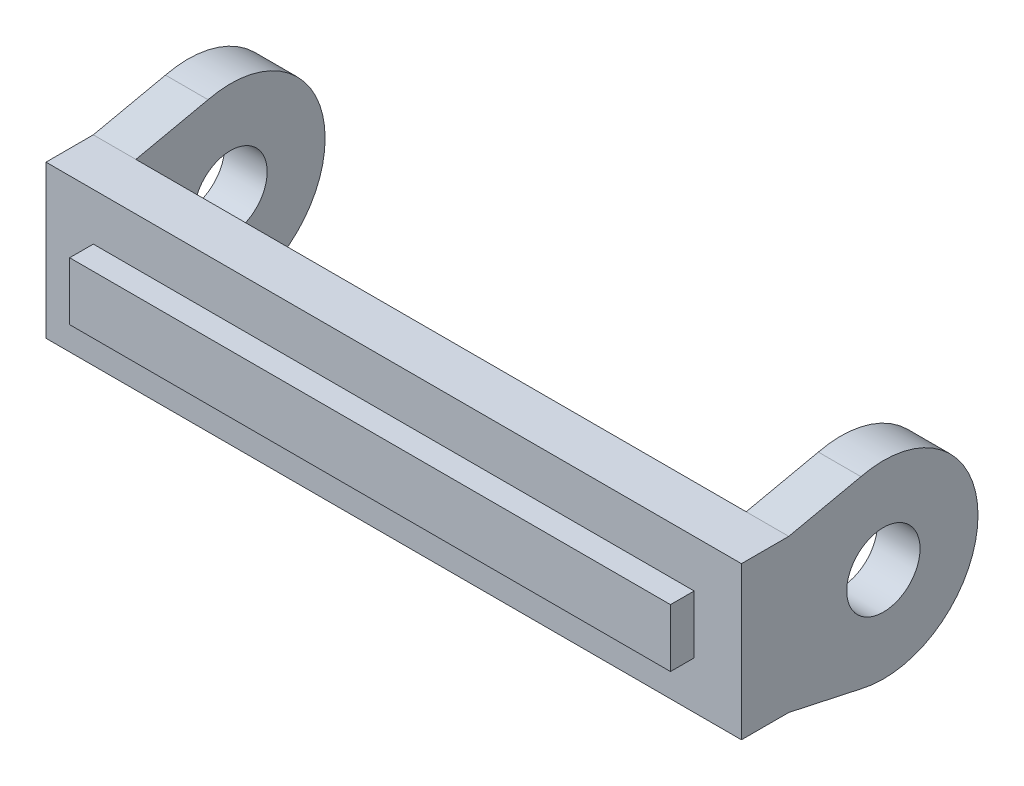
SolidWorks part; units mm, degrees
ref_plane "Alzado" through (0, 0, 0) normal (0, 0, 1) x (1, 0, 0)
ref_plane "Planta" through (0, 0, 0) normal (0, 1, 0) x (1, 0, 0)
ref_plane "Vista lateral" through (0, 0, 0) normal (1, 0, 0) x (0, 0, -1)
sketch "Croquis1" plane through (0, 0, 0) normal (0, 0, 1) x (1, 0, 0)
  line L1 (-35.9671, 18.9928) -> (-9.5671, 18.9928)
  line L2 (-35.9671, 18.9928) -> (-35.9671, 16.0428)
  line L3 (-35.9671, 16.0428) -> (-9.5671, 16.0428)
  line L4 (-9.5671, 18.9928) -> (-9.5671, 16.0428)
  dimension "D1" = 26.4
  dimension "D2" = 2.95
extrude "Saliente-Extruir1" add sketch "Croquis1" along normal blind 1.5
sketch "Croquis2" plane through (-9.5671, 0, 0) normal (1, 0, 0) x (0, 0, -1)
  line L2 (0, 16.0428) -> (0, 18.9928) construction
  line L3 (0, 18.9928) -> (0.3876, 18.9928)
  line L4 (0, 16.0428) -> (0.3876, 16.0428)
  line L6 (-1.5, 16.0428) -> (0, 16.0428) construction
  line L7 (0, 18.9928) -> (-0.5, 18.9928)
  line L9 (0, 16.0428) -> (-0.5, 16.0428)
  line L10 (-0.5, 18.9928) -> (-0.5, 16.0428)
  arc A0 (0.3876, 16.0428) -> (0.3876, 18.9928) centre (3, 17.5178) ccw
  dimension "D1" = 6
  dimension "D2" = 3
  dimension "D3" = 0.5
extrude "Saliente-Extruir2" add sketch "Croquis2" along normal blind 1
sketch "Croquis3" plane through (-35.9671, 0, 0) normal (-1, 0, 0) x (0, 0, 1)
  line L0 (0, 18.9928) -> (0, 16.0428) construction
  line L1 (1.5, 18.9928) -> (0, 18.9928) construction
  line L2 (0.5, 18.9928) -> (-0.3876, 18.9928)
  line L3 (0.5, 18.9928) -> (0.5, 16.0428)
  line L4 (0.5, 16.0428) -> (-0.3876, 16.0428)
  arc A0 (-0.3876, 18.9928) -> (-0.3876, 16.0428) centre (-3, 17.5178) ccw
  dimension "D1" = 6
  dimension "D2" = 3
  dimension "D3" = 0.5
extrude "Saliente-Extruir3" add sketch "Croquis3" along normal blind 1
sketch "Croquis5" plane through (0, 18.9928, 0) normal (0, 1, 0) x (1, 0, 0)
  line L1 (-35.9671, 0.3876) -> (-9.5671, 0.3876)
  line L2 (-35.9671, 0.3876) -> (-35.9671, 0)
  line L3 (-35.9671, 0) -> (-9.5671, 0)
  line L4 (-9.5671, 0.3876) -> (-9.5671, 0)
extrude "Saliente-Extruir4" add sketch "Croquis5" against normal up to surface (2.95 mm away) up to face at (-22.7671, 16.0428, 0.2875)
sketch "Croquis7" plane through (-8.5671, 0, 0) normal (1, 0, 0) x (0, 0, -1)
  circle A0 centre (3, 17.5178) radius 1.5
  dimension "D1" = 3
extrude "Cortar-Extruir1" cut sketch "Croquis7" against normal blind 51
sketch "Croquis8" plane through (-9.5671, 0, 0) normal (-1, 0, 0) x (0, 0, 1)
  circle A0 centre (-3, 17.5178) radius 3
extrude "Cortar-Extruir2" cut sketch "Croquis8" along normal up to surface (26.4 mm away) up to face at (-35.9671, 17.5178, -1.5)
sketch "Croquis9" plane through (0, 0, 0) normal (0, 1, 0) x (1, 0, 0)
  line L0 (-36.9671, -0.5) -> (-35.9671, -0.5) construction
  line L1 (-36.7671, -0.5) -> (-37.2671, -0.5)
  line L2 (-36.7671, -0.5) -> (-36.7671, -1.5)
  line L3 (-36.7671, -1.5) -> (-37.2671, -1.5)
  line L4 (-37.2671, -0.5) -> (-37.2671, -1.5)
  line L5 (-36.9671, -0.5) -> (-36.9671, 0.3876) construction
  line L6 (-8.5671, -0.5) -> (-9.5671, -0.5) construction
  line L7 (-8.7687, -0.5) -> (-8.2687, -0.5)
  line L8 (-8.7687, -0.5) -> (-8.7687, -1.5)
  line L9 (-8.7687, -1.5) -> (-8.2687, -1.5)
  line L10 (-8.2687, -0.5) -> (-8.2687, -1.5)
  line L11 (-8.5671, 0.3876) -> (-8.5671, -0.5) construction
  dimension "D1" = 0.2
  dimension "D2" = 0.5
  dimension "D3" = 0.2017
  dimension "D4" = 0.5
extrude "Saliente-Extruir5" add sketch "Croquis9" along normal blind 20
sketch "Croquis11" plane through (-37.2671, 0, 0) normal (-1, 0, 0) x (0, 0, 1)
  line L1 (0.5, 18.9928) -> (1.5, 18.9928)
  line L2 (0.5, 18.9928) -> (0.5, 20)
  line L3 (0.5, 20) -> (1.5, 20)
  line L4 (1.5, 18.9928) -> (1.5, 20)
  line L5 (0.5, 16.0428) -> (1.5, 16.0428)
  line L6 (0.5, 16.0428) -> (0.5, 0)
  line L7 (0.5, 0) -> (1.5, 0)
  line L8 (1.5, 16.0428) -> (1.5, 0)
extrude "Cortar-Extruir3" cut sketch "Croquis11" against normal blind 40
sketch "Croquis13" plane through (0, 0, 1.5) normal (0, 0, 1) x (1, 0, 0)
  line L0 (-9.5671, 18.9928) -> (-35.9671, 18.9928) construction
  line L1 (-35.4671, 18.7428) -> (-10.0671, 18.7428)
  line L2 (-35.4671, 18.7428) -> (-35.4671, 16.2928)
  line L3 (-35.4671, 16.2928) -> (-10.0671, 16.2928)
  line L4 (-10.0671, 18.7428) -> (-10.0671, 16.2928)
  line L5 (-35.9671, 16.0428) -> (-9.5671, 16.0428) construction
  line L6 (-35.9671, 18.9928) -> (-35.9671, 16.0428) construction
  line L7 (-9.5671, 18.9928) -> (-9.5671, 16.0428) construction
  dimension "D1" = 0.25
  dimension "D2" = 0.25
  dimension "D3" = 0.5
  dimension "D4" = 0.5
extrude "Saliente-Extruir6" add sketch "Croquis13" along normal blind 1
sketch "Croquis14" plane through (0, 18.9928, 0) normal (0, 1, 0) x (1, 0, 0)
  line L1 (-35.9671, -0.5) -> (-40.4942, -0.5)
  line L2 (-35.9671, -0.5) -> (-35.9671, -2.0892)
  line L3 (-35.9671, -2.0892) -> (-40.4942, -2.0892)
  line L4 (-40.4942, -0.5) -> (-40.4942, -2.0892)
  line L5 (-9.5671, -0.5) -> (-6.2413, -0.5)
  line L6 (-9.5671, -0.5) -> (-9.5671, -2.6891)
  line L7 (-9.5671, -2.6891) -> (-6.2413, -2.6891)
  line L8 (-6.2413, -0.5) -> (-6.2413, -2.6891)
extrude "Cortar-Extruir4" cut sketch "Croquis14" against normal blind 21
sketch "Croquis16" plane through (0, 18.9928, 0) normal (0, 1, 0) x (1, 0, 0)
  line L1 (-7.5159, -1.5) -> (-41.9143, -1.5)
  line L2 (-7.5159, -1.5) -> (-7.5159, 7.9216)
  line L3 (-7.5159, 7.9216) -> (-41.9143, 7.9216)
  line L4 (-41.9143, -1.5) -> (-41.9143, 7.9216)
extrude "Cortar-Extruir5" cut sketch "Croquis16" against normal blind 21 and the other way blind 21
sketch "Croquis17" plane through (0, 0, 1.5) normal (0, 0, -1) x (-1, 0, 0)
  line L0 (10.0671, 18.7428) -> (35.4671, 18.7428) construction
  line L1 (8.0671, 20.7428) -> (37.4671, 20.7428)
  line L2 (8.0671, 20.7428) -> (8.0671, 14.2928)
  line L3 (8.0671, 14.2928) -> (37.4671, 14.2928)
  line L4 (37.4671, 20.7428) -> (37.4671, 14.2928)
  line L5 (35.4671, 16.2928) -> (10.0671, 16.2928) construction
  line L6 (10.0671, 16.2928) -> (10.0671, 18.7428) construction
  line L7 (35.4671, 18.7428) -> (35.4671, 16.2928) construction
  dimension "D1" = 2
  dimension "D2" = 2
  dimension "D3" = 2
  dimension "D4" = 2
extrude "Saliente-Extruir7" add sketch "Croquis17" along normal blind 2
sketch "Croquis18" plane through (-8.0671, 0, 0) normal (1, 0, 0) x (0, 0, -1)
  line L0 (0.5, 20.7428) -> (0.5, 14.2928) construction
  line L1 (0.5, 20.7428) -> (3.5506, 21.4035)
  line L3 (3.5506, 13.6321) -> (0.5, 14.2928)
  line L4 (0.5, 14.2928) -> (0.5, 20.7428)
  arc A0 (3.5506, 13.6321) -> (3.5506, 21.4035) centre (4.5, 17.5178) ccw
  circle A1 centre (4.5, 17.5178) radius 1.55
  point P4 (0.5, 17.5178)
  dimension "D1" = 8
  dimension "D2" = 4
  dimension "D3" = 0
  dimension "D4" = 3.1
extrude "Saliente-Extruir8" add sketch "Croquis18" against normal up to surface (29.4 mm away) up to face at (-37.4671, 17.5178, 0.5)
sketch "Croquis19" plane through (0, 20.7428, 0) normal (0, 1, 0) x (1, 0, 0)
  line L0 (-37.4671, 0.5) -> (-8.0671, 0.5) construction
  line L1 (-35.6671, 0.5) -> (-9.8671, 0.5)
  line L2 (-35.6671, 0.5) -> (-35.6671, 11.079)
  line L3 (-35.6671, 11.079) -> (-9.8671, 11.079)
  line L4 (-9.8671, 0.5) -> (-9.8671, 11.079)
  line L5 (-8.0671, 3.5506) -> (-8.0671, 8.5) construction
  dimension "D1" = 25.8
  dimension "D2" = 1.8
extrude "Cortar-Extruir6" cut sketch "Croquis19" against normal blind 32 and the other way blind 12
